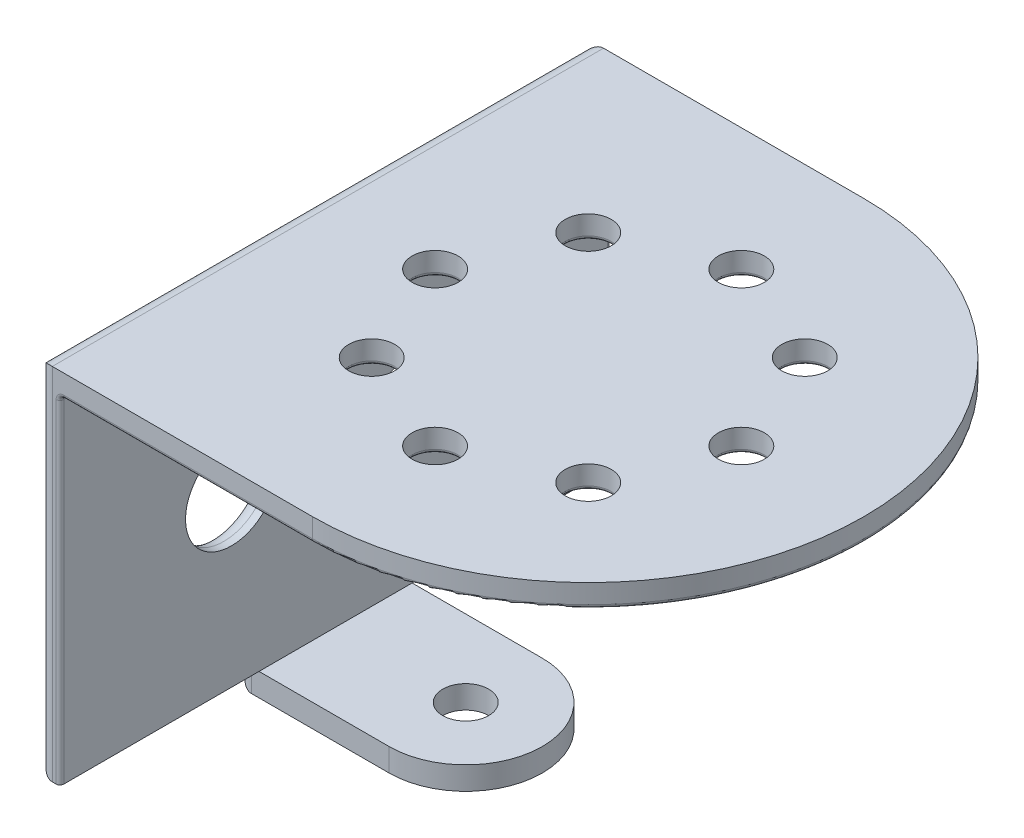
SolidWorks part; units mm, degrees
material "PLA"
ref_plane "Alzado" through (0, 0, 0) normal (0, 0, 1) x (1, 0, 0)
ref_plane "Planta" through (0, 0, 0) normal (0, 1, 0) x (1, 0, 0)
ref_plane "Vista lateral" through (0, 0, 0) normal (1, 0, 0) x (0, 0, -1)
sketch "Croquis1" plane through (0, 0, 0) normal (1, 0, 0) x (0, 0, -1)
  line L0 (18, 0) -> (-18, 0) construction
  line L1 (-18, -11) -> (18, -11)
  line L2 (-18, -11) -> (-18, 11)
  line L3 (-18, 11) -> (18, 11)
  line L4 (18, -11) -> (18, 11)
  line L5 (-18, -11) -> (18, 11) construction
  line L6 (-18, 11) -> (18, -11) construction
  circle A0 centre (13.8, 8.75) radius 1.5
  circle A1 centre (-6.8, 0) radius 3
  circle A2 centre (13.8, -8.75) radius 1.5
  circle A3 centre (4.2, 0) radius 1.75
  point P0 (0, 0)
  dimension "D3" = 4.2
  dimension "D5" = 3
  dimension "D6" = 6
  dimension "D8" = 13.8
  dimension "D9" = 3.5
  dimension "D1" = 22
  dimension "D2" = 36
  dimension "D4" = 2.25
  dimension "D7" = 11.2
extrude "Saliente-Extruir1" add sketch "Croquis1" along normal blind 1.5
sketch "Croquis3" plane through (0, -11, 0) normal (0, -1, 0) x (1, 0, 0)
  line L0 (0, 18) -> (0, -18) construction
  line L1 (18, -18) -> (0, -18)
  line L2 (18, 18) -> (0, 18)
  line L3 (0, 18) -> (0, -18)
  arc A0 (18, -18) -> (18, 18) centre (18, 0) ccw
  point P1 (0, 0)
  point P8 (0, 26.3991)
  dimension "D1" = 36
  dimension "D2" = 18
extrude "Extruir-Lámina1" [suppressed] add sketch "Croquis3" along normal blind 1.5 separate body thin thin type one direction wall 10
extrude "Saliente-Extruir3" add sketch "Croquis3<2>" against normal blind 1.5 from surface starting at face at (0.75, 11, 0)
sketch "Croquis3<2>" plane through (0, -11, 0) normal (0, -1, 0) x (1, 0, 0) same geometry as "Croquis3"
sketch "Croquis4" plane through (0, 11, 0) normal (0, 1, 0) x (1, 0, 0)
  line L3 (10, 5) -> (0, 5)
  line L4 (0, -18) -> (0, 18) construction
  line L5 (10, -5) -> (0, -5)
  line L6 (0, -5) -> (0, 5)
  arc A0 (10, -5) -> (10, 5) centre (10, 0) ccw
  dimension "D1" = 10
  dimension "D2" = 10
extrude "Saliente-Extruir4" add sketch "Croquis4" against normal blind 1.5 from surface starting at face at (0.75, -11, 0)
sketch "Croquis5" plane through (0, -12.5, 0) normal (0, -1, 0) x (-1, 0, 0)
  circle A0 centre (-10, 0) radius 1.5
  dimension "D1" = 3
extrude "Cortar-Extruir1" cut sketch "Croquis5" against normal up to next
sketch "Croquis7" plane through (0, 12.5, 0) normal (0, 1, 0) x (-1, 0, 0)
  line L0 (-18, 0) -> (0, 0) construction
  arc A0 (-18, 18) -> (-18, -18) centre (-18, 0) ccw construction
  circle A1 centre (-8, 0) radius 1.5
  circle A2 centre (-10.9289, -7.0711) radius 1.5
  circle A3 centre (-18, -10) radius 1.5
  circle A4 centre (-25.0711, -7.0711) radius 1.5
  circle A5 centre (-28, 0) radius 1.5
  circle A6 centre (-25.0711, 7.0711) radius 1.5
  circle A7 centre (-18, 10) radius 1.5
  circle A8 centre (-10.9289, 7.0711) radius 1.5
  point P8 (18, 0)
  point P25 (-18, 0)
  dimension "D1" = 3
  dimension "D2" = 10
  dimension "D4" = 8
  dimension "D3" = 8
extrude "Cortar-Extruir2" cut sketch "Croquis7" against normal up to next
fillet "Redondeo1" [suppressed] radius 1
fillet "Redondeo2" radius 1 12 edges at (0, 0, -5.95) (0, 0, 3.8) (0, 0.75, 18) (0, 12.5, 0) (0, 0.75, -18) (0, 8.75, -15.3) (0, -8.75, -12.3) (0, -11, 11.5) (0, -11.75, 5) (0, -12.5, 0) (0, -11.75, -5) (0, -11, -11.5)
fillet "Redondeo3" radius 0.25 14 edges at (1.5, 0, -18) (1.5, 0, 18) (9.75, 11, -18) (36, 11, 0) (9.75, 11, 18) (1.5, 11, 0) (8, 11, -1.5) (10.9289, 11, -8.5711) (18, 11, -11.5) (25.0711, 11, -8.5711) (28, 11, -1.5) (25.0711, 11, 5.5711) (18, 11, 8.5) (10.9289, 11, 5.5711)
